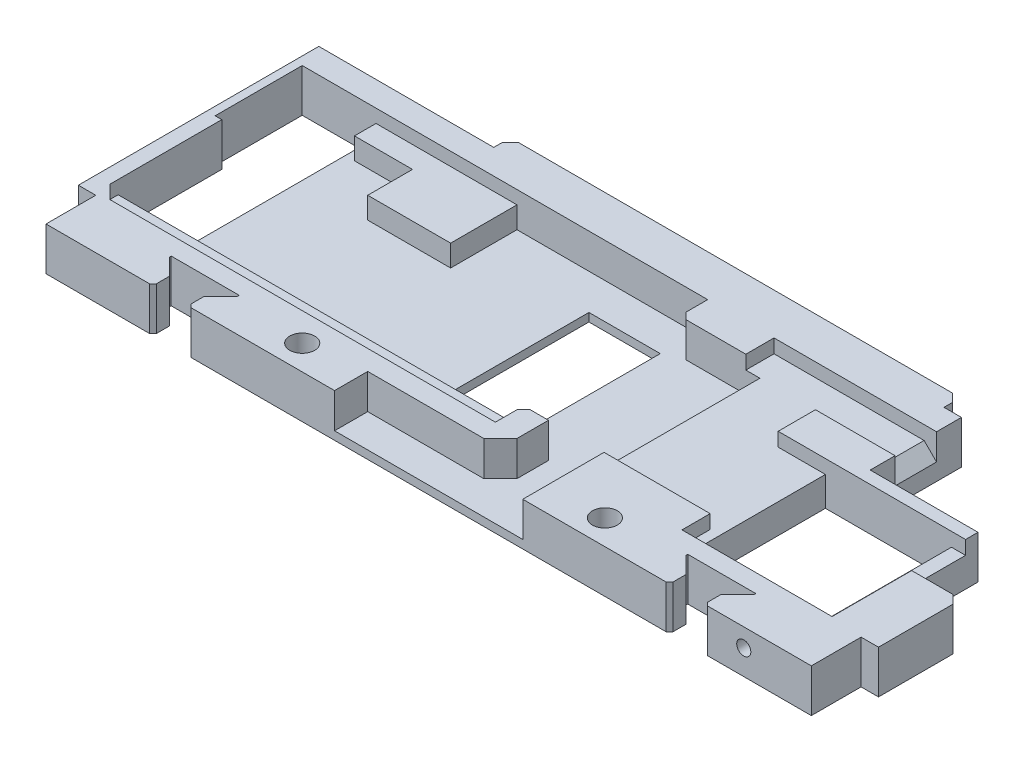
SolidWorks part; units mm, degrees
ref_plane "前视基准面" through (0, 0, 0) normal (0, 0, 1) x (1, 0, 0)
ref_plane "上视基准面" through (0, 0, 0) normal (0, 1, 0) x (1, 0, 0)
ref_plane "右视基准面" through (0, 0, 0) normal (1, 0, 0) x (0, 0, -1)
sketch "草图1" plane through (0, 0, 0) normal (0, 1, 0) x (1, 0, 0)
  line L1 (0, 0) -> (96.5, 0) construction
  line L2 (0, 0) -> (0, 35) construction
  line L3 (0, 35) -> (96.5, 35)
  line L4 (96.5, 0) -> (96.5, 35) construction
  line L5 (0, 35) -> (0, 0)
  line L7 (0, 0) -> (96.5, 0)
  line L10 (96.5, 35) -> (96.5, 0)
  dimension "D1" = 96.5
  dimension "D2" = 35
extrude "凸台-拉伸1" add sketch "草图1" along normal blind 5.2
sketch "草图4" plane through (0, 5.2, 0) normal (0, 1, 0) x (1, 0, 0)
  line L0 (0, 35) -> (0, 0) construction
  line L1 (1.8, 6.4) -> (49.9, 6.4)
  line L2 (1.8, 6.4) -> (1.8, 32)
  line L3 (1.8, 32) -> (49.9, 32)
  line L4 (49.9, 6.4) -> (49.9, 9.8)
  line L5 (0, 0) -> (96.5, 0) construction
  line L6 (49.9, 28.6) -> (49.9, 32)
  line L7 (49.9, 28.6) -> (57.9, 28.6)
  line L9 (49.9, 9.8) -> (57.9, 9.8)
  line L10 (57.9, 28.6) -> (57.9, 9.8)
  dimension "D1" = 1.8
  dimension "D2" = 6.4
  dimension "D3" = 25.6
  dimension "D4" = 48.1
  dimension "D5" = 3.4
  dimension "D6" = 3.4
  dimension "D7" = 8
extrude "切除-拉伸6" cut sketch "草图4" against normal blind 1.6
sketch "草图5" plane through (0, 3.6, 0) normal (0, 1, 0) x (1, 0, 0)
  line L0 (49.9, 9) -> (1.8, 9)
  line L3 (1.8, 6.4) -> (49.9, 6.4) construction
  line L4 (16.9, 29.4) -> (9.9, 29.4)
  line L6 (16.9, 29.4) -> (16.9, 24)
  line L7 (16.9, 24) -> (26.9, 24)
  line L8 (1.8, 32) -> (1.8, 6.4)
  line L9 (1.8, 6.4) -> (49.9, 6.4)
  line L10 (49.9, 6.4) -> (49.9, 9.8)
  line L11 (49.9, 9.8) -> (57.9, 9.8)
  line L12 (57.9, 9.8) -> (57.9, 28.6)
  line L13 (57.9, 28.6) -> (49.9, 28.6)
  line L14 (49.9, 28.6) -> (49.9, 32)
  line L15 (49.9, 32) -> (1.8, 32)
  line L16 (1.8, 32) -> (1.8, 9)
  line L18 (49.9, 9) -> (49.9, 9.8)
  line L19 (49.9, 9.8) -> (57.9, 9.8)
  line L20 (57.9, 9.8) -> (57.9, 28.6)
  line L21 (57.9, 28.6) -> (49.9, 28.6)
  line L22 (49.9, 28.6) -> (49.9, 32)
  line L23 (9.9, 32) -> (1.8, 32)
  line L24 (26.9, 32) -> (26.9, 24)
  line L25 (9.9, 29.4) -> (9.9, 32)
  line L26 (26.9, 32) -> (49.9, 32)
  dimension "D2" = 2.6
  dimension "D3" = 10
  dimension "D4" = 2.6
  dimension "D5" = 8
  dimension "D6" = 23
  dimension "D7" = 17
  dimension "D1" = 0
extrude "切除-拉伸7" cut sketch "草图5" against normal blind 2.6
sketch "草图6" plane through (0, 1, 0) normal (0, 1, 0) x (1, 0, 0)
  line L0 (3.8, 32) -> (8.8, 32)
  line L3 (1, 32) -> (1, 21.5)
  line L4 (1, 21.5) -> (1.8, 21.5)
  line L7 (3.8, 32) -> (1, 32)
  line L9 (9.9, 32) -> (1.8, 32) construction
  line L11 (0, 35) -> (0, 0) construction
  line L12 (8.8, 32) -> (8.8, 9)
  line L13 (1.8, 9) -> (49.9, 9) construction
  line L14 (1.8, 9) -> (8.8, 9)
  line L15 (1.8, 32) -> (1.8, 9) construction
  line L16 (1.8, 21.5) -> (1.8, 9)
  line L17 (49.9, 32) -> (1.8, 32) construction
  dimension "D3" = 1
  dimension "D4" = 10.5
  dimension "D5" = 7
extrude "切除-拉伸15" cut sketch "草图6" against normal mid plane 10
sketch "草图7" plane through (0, 1, 0) normal (0, 1, 0) x (1, 0, 0)
  line L1 (39.879, 27.7) -> (47.879, 27.7)
  line L2 (39.879, 27.7) -> (39.879, 10.7)
  line L3 (39.879, 10.7) -> (47.879, 10.7)
  line L4 (47.879, 27.7) -> (47.879, 10.7)
  line L5 (49.9, 32) -> (1, 32) construction
  line L6 (51.879, 32) -> (51.879, 28.19) construction
  dimension "D1" = 17
  dimension "D2" = 4.3
  dimension "D3" = 12
  dimension "D4" = 8
extrude "切除-拉伸16" cut sketch "草图7" against normal through all
sketch "草图8" plane through (0, 5.2, 0) normal (0, 1, 0) x (1, 0, 0)
  line L0 (1.8, 6.4) -> (49.9, 6.4) construction
  line L1 (72.4, 22.5) -> (90.5, 22.5)
  line L2 (72.4, 22.5) -> (72.4, 6.4)
  line L3 (72.4, 6.4) -> (90.5, 6.4)
  line L4 (90.5, 22.5) -> (90.5, 6.4)
  line L5 (49.9, 6.4) -> (49.9, 9.8) construction
  dimension "D1" = 16.1
  dimension "D2" = 18.1
  dimension "D3" = 0
  dimension "D4" = 22.5
extrude "切除-拉伸17" cut sketch "草图8" against normal blind 1.66
sketch "草图9" plane through (0, 3.54, 0) normal (0, 1, 0) x (1, 0, 0)
  line L0 (90.5, 22.5) -> (72.4, 22.5) construction
  line L1 (73.6, 22.5) -> (88.8, 22.5)
  line L2 (73.6, 22.5) -> (73.6, 6.4)
  line L3 (73.6, 6.4) -> (88.8, 6.4)
  line L4 (88.8, 22.5) -> (88.8, 6.4)
  line L5 (72.4, 6.4) -> (90.5, 6.4) construction
  line L6 (72.4, 22.5) -> (72.4, 6.4) construction
  line L7 (90.5, 6.4) -> (90.5, 22.5) construction
  dimension "D1" = 1.2
  dimension "D2" = 1.7
extrude "切除-拉伸18" cut sketch "草图9" against normal up to next
chamfer "倒角1" distance 0.6 angle 45 1 edges at (47.879, 1, -19.2)
sketch "草图10" plane through (0, 5.2, 0) normal (0, 1, 0) x (1, 0, 0)
  line L1 (72.4, 22.5) -> (57.9, 22.5)
  line L2 (72.4, 22.5) -> (72.4, 9.8)
  line L3 (72.4, 9.8) -> (57.9, 9.8)
  line L4 (57.9, 22.5) -> (57.9, 9.8)
extrude "切除-拉伸19" cut sketch "草图10" against normal up to surface (1.66 mm away) up to face at (73, 3.54, -14.45)
chamfer "倒角2" distance 0.8 angle 45 2 edges at (49.9, 3.1, -28.6) (49.9, 3.1, -9.8)
sketch "草图12" plane through (0, 5.2, 0) normal (0, 1, 0) x (1, 0, 0)
  line L0 (90.5, 6.4) -> (90.5, 22.5) construction
  line L1 (96.5, 35) -> (77.5, 35)
  line L2 (96.5, 35) -> (96.5, 16)
  line L3 (90.5, 24) -> (77.5, 24)
  line L4 (77.5, 35) -> (77.5, 24)
  line L7 (96.5, 16) -> (90.5, 16)
  line L8 (90.5, 24) -> (90.5, 16)
  dimension "D1" = 11
  dimension "D2" = 19
  dimension "D3" = 19
extrude "切除-拉伸20" cut sketch "草图12" against normal through all
chamfer "倒角4" distance 1 angle 45 1 edges at (96.5, 2.6, -16)
sketch "草图14" plane through (0, 5.2, 0) normal (0, 1, 0) x (1, 0, 0)
  line L0 (77.5, 35) -> (0, 35) construction
  line L1 (21.1, 35) -> (75.4, 35)
  line L2 (21.1, 35) -> (21.1, 37)
  line L3 (21.1, 37) -> (75.4, 37)
  line L4 (75.4, 35) -> (75.4, 37)
  line L5 (0, 35) -> (0, 0) construction
  line L6 (96.5, 0) -> (96.5, 15) construction
  dimension "D1" = 21.1
  dimension "D2" = 21.1
  dimension "D3" = 2
extrude "凸台-拉伸2" add sketch "草图14" against normal up to surface (5.2 mm away) up to face at (81.2, 0, -14.45)
chamfer "倒角5" distance 1 angle 45 2 edges at (75.4, 2.6, -37) (21.1, 2.6, -37)
sketch "草图15" plane through (0, 5.2, 0) normal (0, 1, 0) x (1, 0, 0)
  line L0 (77.5, 35) -> (77.5, 24) construction
  line L1 (77.5, 32) -> (57.9, 32)
  line L2 (77.5, 32) -> (77.5, 27)
  line L3 (77.5, 27) -> (67.9, 27)
  line L4 (57.9, 32) -> (57.9, 30.6025)
  line L5 (57.9, 9.8) -> (57.9, 28.6) construction
  line L6 (90.5, 22.5) -> (57.9, 22.5) construction
  line L8 (57.9, 30.6025) -> (57.9, 22.5)
  line L9 (57.9, 22.5) -> (67.9, 22.5)
  line L10 (67.9, 27) -> (67.9, 22.5)
  line L11 (77.5, 35) -> (75.4, 35) construction
  point P15 (57.9, 26.5512)
  dimension "D1" = 3
  dimension "D2" = 5
  dimension "D3" = 10
extrude "切除-拉伸21" cut sketch "草图15" against normal up to surface (1.66 mm away) up to face at (89.82, 3.54, -14.76)
chamfer "倒角3" distance 1.5 angle 45 1 edges at (77.5, 3.54, -29.5)
chamfer "倒角6" distance 1.6 angle 45 1 edges at (1.8, 4.4, -6.4)
sketch "草图16" plane through (0, 5.2, 0) normal (0, 1, 0) x (1, 0, 0)
  line L1 (0, 0) -> (2.1, 0)
  line L2 (0, 0) -> (0, 6)
  line L3 (0, 6) -> (2.1, 6)
  line L4 (2.1, 0) -> (2.1, 6)
  line L5 (96.5, 0) -> (94.4, 0)
  line L6 (96.5, 0) -> (96.5, 6)
  line L7 (96.5, 6) -> (94.4, 6)
  line L8 (94.4, 0) -> (94.4, 6)
  dimension "D1" = 6
  dimension "D2" = 2.1
extrude "切除-拉伸22" cut sketch "草图16" against normal through all
sketch "草图19" plane through (0, 5.2, 0) normal (0, 1, 0) x (1, 0, 0)
  line L0 (2.1, 0) -> (94.4, 0) construction
  line L3 (15, 0) -> (19.2, 0)
  line L5 (2.1, 0) -> (2.1, 6) construction
  line L6 (94.4, 6) -> (94.4, 0) construction
  line L7 (17.1, 8.32) -> (17.1, -2.6088) construction
  line L9 (77.3, 2) -> (77.3, 0)
  line L10 (77.3, 0) -> (81.5, 0)
  line L14 (13, 2) -> (15, 2)
  line L15 (13, 2) -> (13, 4.2)
  line L16 (13, 4.2) -> (21.2, 4.2)
  line L17 (21.2, 2) -> (21.2, 4.2)
  line L18 (13, 2) -> (21.2, 4.2) construction
  line L19 (13, 4.2) -> (21.2, 2) construction
  line L20 (75.3, 2) -> (77.3, 2)
  line L21 (75.3, 2) -> (75.3, 4.2)
  line L22 (75.3, 4.2) -> (83.5, 4.2)
  line L23 (83.5, 2) -> (83.5, 4.2)
  line L24 (75.3, 2) -> (83.5, 4.2) construction
  line L25 (75.3, 4.2) -> (83.5, 2) construction
  line L26 (79.4, -2.3924) -> (79.4, 10.1048) construction
  line L27 (15, 2) -> (15, 0)
  line L28 (19.2, 2) -> (19.2, 0)
  line L29 (19.2, 2) -> (21.2, 2)
  line L30 (81.5, 2) -> (83.5, 2)
  line L31 (81.5, 2) -> (81.5, 0)
  point P0 (24.5613, 2.8556)
  point P7 (79.4, 3.8562)
  point P12 (17.1, 3.1)
  point P17 (79.4, 3.1)
  point P26 (17.1, 2.8556)
  point P30 (79.4, 3.8562)
  dimension "D1" = 4.2
  dimension "D2" = 2.2
  dimension "D3" = 2
  dimension "D4" = 8.2
  dimension "D5" = 15
  dimension "D6" = 15
extrude "切除-拉伸24" cut sketch "草图19" against normal through all
chamfer "倒角11" distance 2 angle 45 4 edges at (83.5, 2.6, -2) (75.3, 2.6, -2) (21.2, 2.6, -2) (13, 2.6, -2)
chamfer "倒角10" distance 0.4 angle 45 4 edges at (81.5, 2.6, 0) (77.3, 2.6, 0) (15, 2.6, 0) (19.2, 2.6, 0)
sketch "草图21" plane through (0, 5.2, 0) normal (0, 1, 0) x (1, 0, 0)
  line L0 (50.7, 9.8) -> (72.4, 9.8) construction
  line L1 (52.9, 9.8) -> (59.6, 9.8)
  line L2 (52.9, 9.8) -> (52.9, 0)
  line L3 (52.9, 0) -> (59.6, 0)
  line L4 (59.6, 9.8) -> (59.6, 0)
  line L5 (19.6, 0) -> (76.9, 0) construction
  line L6 (49.9, 6.4) -> (49.9, 9) construction
  dimension "D1" = 6.7
  dimension "D2" = 3
extrude "切除-拉伸26" cut sketch "草图21" against normal up to surface (4.2 mm away) up to face at (44.179, 1, -19.2)
chamfer "倒角9" distance 1.7 angle 45 2 edges at (57.9, 3.54, -19.2) (58.75, 3.54, -9.8)
sketch "草图22" plane through (0, 5.2, 0) normal (0, 1, 0) x (1, 0, 0)
  line L1 (52.9, 0) -> (36.9, 0)
  line L2 (52.9, 0) -> (52.9, 4)
  line L3 (52.9, 4) -> (36.9, 4)
  line L4 (36.9, 0) -> (36.9, 4)
  dimension "D1" = 16
  dimension "D2" = 4
extrude "切除-拉伸27" cut sketch "草图22" against normal up to surface (4.2 mm away) up to face at (44.179, 1, -19.2)
chamfer "倒角12" distance 2 angle 45 1 edges at (52.9, 3.1, -4)
sketch "草图24" plane through (0, 5.2, 0) normal (0, 1, 0) x (1, 0, 0)
  circle A0 centre (66.5, 3) radius 1.2 construction
  circle A1 centre (30, 3) radius 1.2 construction
  circle A2 centre (66.5, 3) radius 1.2 construction
  circle A3 centre (30, 3) radius 1.2 construction
  circle A4 centre (30, 3) radius 1.5
  circle A5 centre (66.5, 3) radius 1.5
  dimension "D1" = 3
extrude "切除-拉伸28" cut sketch "草图24" against normal through all
sketch "草图25" plane through (0, 0, -35) normal (0, 0, -1) x (-1, 0, 0)
  circle A0 centre (-10.2, 2.6) radius 1.2 construction
  circle A1 centre (-10.2, 2.6) radius 1.2 construction
  circle A2 centre (-10.2, 2.6) radius 0.85
  dimension "D1" = 1.7
extrude "切除-拉伸29" cut sketch "草图25" against normal blind 3
sketch "草图26" plane through (0, 0, 0) normal (0, 0, 1) x (1, 0, 0)
  circle A0 centre (86.25, 3) radius 1.2 construction
  circle A1 centre (86.25, 3) radius 1.2 construction
  circle A2 centre (86.25, 3) radius 0.85
  dimension "D1" = 1.7
extrude "切除-拉伸30" cut sketch "草图26" against normal blind 4
equation "\"0，8\"=1"
